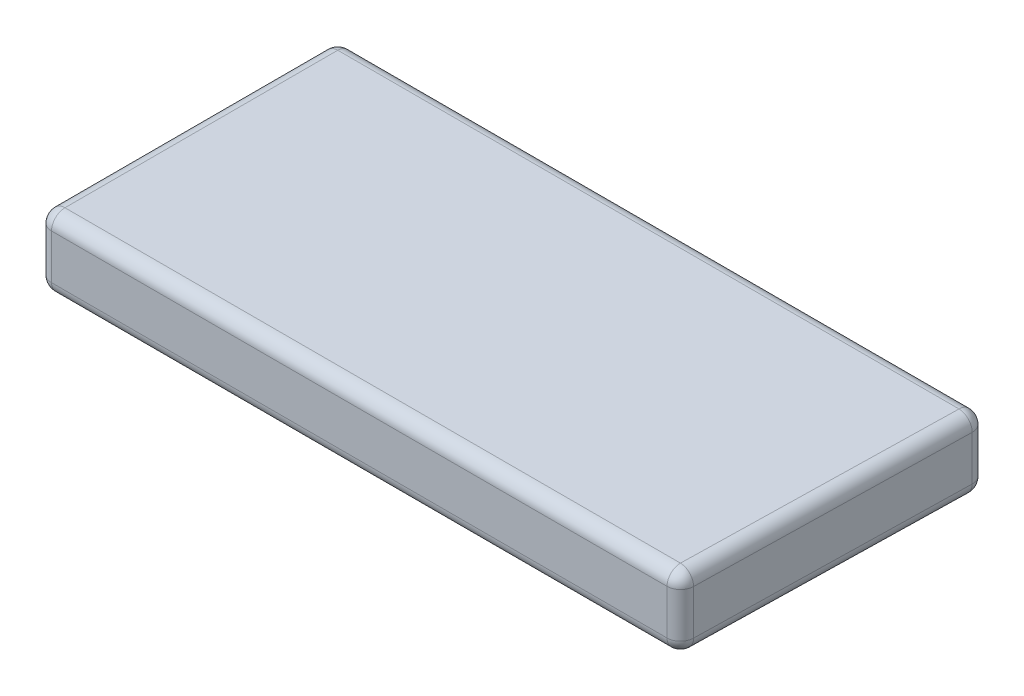
SolidWorks part; units mm, degrees
ref_plane "Front Plane" through (0, 0, 0) normal (0, 0, 1) x (1, 0, 0)
ref_plane "Top Plane" through (0, 0, 0) normal (0, 1, 0) x (1, 0, 0)
ref_plane "Right Plane" through (0, 0, 0) normal (1, 0, 0) x (0, 0, -1)
sketch "Sketch2" plane through (0, 0, 0) normal (0, 1, 0) x (1, 0, 0)
  line L4 (-72.4956, -0.7992) -> (-72.4956, 33.5)
  line L5 (-72.4956, 33.5) -> (72.4956, 33.5)
  line L6 (72.4956, 33.5) -> (71.0702, -33.5)
  line L7 (71.0702, -33.5) -> (-72.4956, -33.5)
  line L8 (-72.4956, -33.5) -> (-72.4956, -0.7992)
extrude "Boss-Extrude2" add sketch "Sketch2" along normal blind 8 and the other way blind 8 contours L5 L6 L7 L8 L4
sketch "Sketch3" plane through (-72.4956, 0, 0) normal (-1, 0, 0) x (0, 0, 1)
  line L0 (-33.5, -8) -> (-33.5, 8) construction
  line L2 (-23.5, -2.4283) -> (-23.5, 2.5717)
  line L3 (-23.5, 2.5717) -> (-11, 2.5717)
  line L4 (-11, 2.5717) -> (-11, -2.4283)
  line L5 (-11, -2.4283) -> (-23.5, -2.4283)
  line L6 (23.5, -2.4283) -> (23.5, 2.5717)
  line L7 (23.5, 2.5717) -> (11, 2.5717)
  line L8 (11, 2.5717) -> (11, -2.4283)
  line L9 (11, -2.4283) -> (23.5, -2.4283)
  line L10 (33.5, -8) -> (33.5, 8) construction
  line L14 (-2.9886, 1.301) -> (2.9303, 1.301)
  line L15 (2.9303, 1.301) -> (2.9303, -1.1954)
  line L16 (2.9303, -1.1954) -> (-2.9886, -1.1954)
  line L17 (-2.9886, -1.1954) -> (-2.9886, 1.301)
  point P2 (-33.5, 0)
  point P14 (0, 0)
  dimension "D1" = 10
  dimension "D2" = 12.5
  dimension "D3" = 5
  dimension "D4" = 12.5
  dimension "D5" = 5
  dimension "D6" = 10
extrude "Cut-Extrude1" cut sketch "Sketch3" against normal blind 8
fillet "Fillet1" radius 3 12 edges at (72.4956, 0, -33.5) (0, 8, -33.5) (-72.4956, 0, -33.5) (71.7829, -8, 0) (0, -8, -33.5) (-72.4956, -8, 0) (-0.7127, -8, 33.5) (-72.4956, 0, 33.5) (-0.7127, 8, 33.5) (71.0702, 0, 33.5) (71.7829, 8, 0) (-72.4956, 8, 0)
fillet "Fillet2" radius 1 8 edges at (-72.4956, 0.0717, 11) (-72.4956, 2.5717, 17.25) (-72.4956, 0.0717, 23.5) (-72.4956, -2.4283, 17.25) (-72.4956, -2.4283, -17.25) (-72.4956, 0.0717, -23.5) (-72.4956, 2.5717, -17.25) (-72.4956, 0.0717, -11)
fillet "Fillet3" radius 0.5 4 edges at (-72.4956, 1.301, -0.0291) (-72.4956, 0.0528, -2.9886) (-72.4956, -1.1954, -0.0291) (-72.4956, 0.0528, 2.9303)
